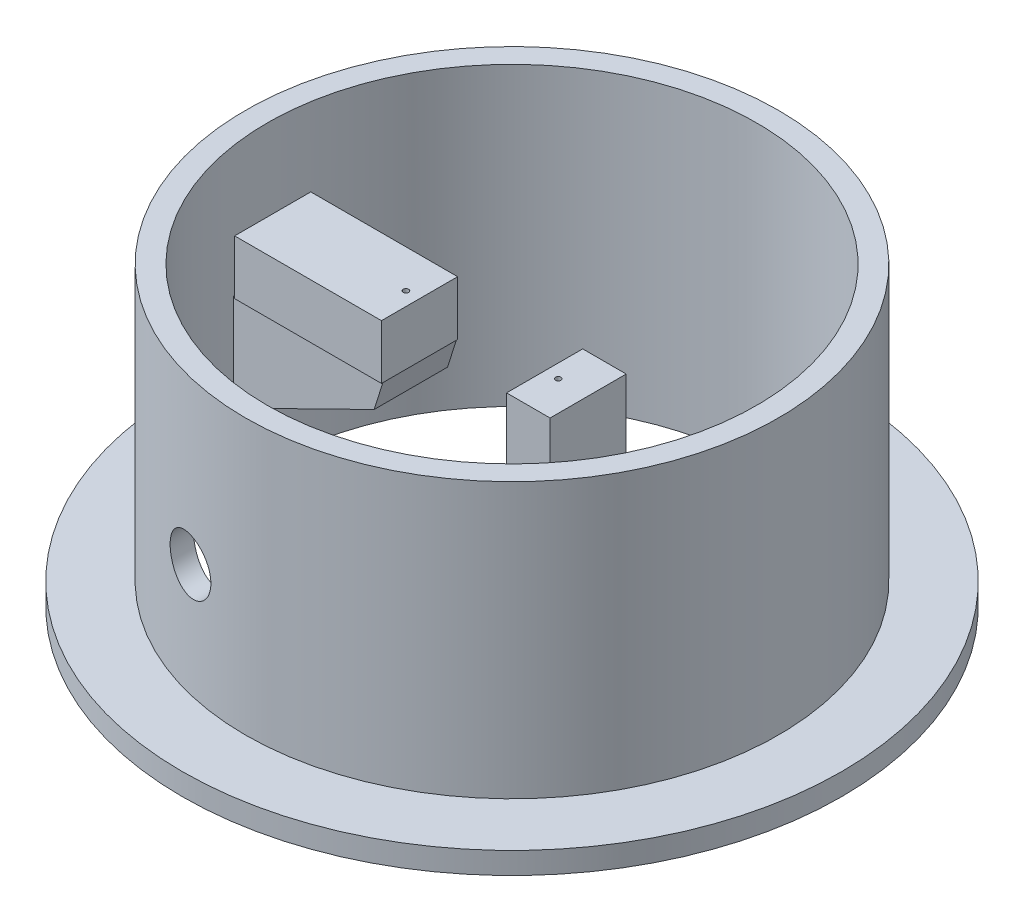
SolidWorks part; units mm, degrees
ref_plane "Front Plane" through (0, 0, 0) normal (0, 0, 1) x (1, 0, 0)
ref_plane "Top Plane" through (0, 0, 0) normal (0, 1, 0) x (1, 0, 0)
ref_plane "Right Plane" through (0, 0, 0) normal (1, 0, 0) x (0, 0, -1)
sketch "Sketch1" plane through (0, 0, 0) normal (0, 1, 0) x (1, 0, 0)
  circle A0 centre (0, 0) radius 60.625
  circle A1 centre (0, 0) radius 45
  dimension "D1" = 121.25
  dimension "D2" = 90
extrude "Boss-Extrude1" add sketch "Sketch1" along normal blind 4
sketch "Sketch2" plane through (0, 4, 0) normal (0, 1, 0) x (1, 0, 0)
  circle A0 centre (0, 0) radius 45 construction
  circle A1 centre (0, 0) radius 45
  circle A2 centre (0, 0) radius 49
  dimension "D1" = 4
extrude "Boss-Extrude2" add sketch "Sketch2" along normal blind 50.5
ref_plane "Plane1" through (0, 34.5, 0) normal (0, 1, 0) x (1, 0, 0)
sketch "Sketch4" plane through (0, 0, 0) normal (0, 0, 1) x (1, 0, 0)
  line L0 (-60.625, 0) -> (60.625, 0) construction
  line L1 (6, 40.5) -> (14, 40.5)
  line L2 (6, 40.5) -> (6, 0)
  line L3 (6, 0) -> (14, 0)
  line L4 (14, 40.5) -> (14, 0)
  line L5 (49, 54.5) -> (-49, 54.5) construction
  line L6 (-45, 54.5) -> (-45, 4)
  line L7 (-17, 40.5) -> (-44, 40.5)
  line L8 (-17, 40.5) -> (-17, 30.5)
  line L9 (-17, 30.5) -> (-44, 30.5)
  line L10 (-44, 40.5) -> (-44, 30.5)
  line L11 (60.625, 4) -> (-60.625, 4) construction
  line L12 (-17, 30.5) -> (-45, 2.5)
  dimension "D1" = 6
  dimension "D2" = 8
  dimension "D3" = 14
  dimension "D4" = 23
  dimension "D5" = 27
  dimension "D6" = 10
  dimension "D7" = 45
  dimension "D8" = 14
extrude "Boss-Extrude4" add sketch "Sketch4" along normal mid plane 14 contours L9 L8 L7 L6 | L12 L9 L6 | L1 L4 L3 L2 region at (-30.5, 35.5, 0)
sketch "Sketch5" plane through (0, 0, 0.8324) normal (0, -1, 0) x (1, 0, 0)
  line L0 (0.9227, 14.5796) -> (36.1058, 30.1379)
  line L1 (0.9227, -16.0291) -> (36.6512, -32.9046)
  line L2 (0.9227, 14.5796) -> (0.9227, -16.0291)
  arc A1 (36.6512, -32.9046) -> (36.1058, 30.1379) centre (-2.8733, -1.7229) ccw
extrude "Boss-Extrude5" add sketch "Sketch5" against normal up to surface (4 mm away) contours L0 A1 L1 L2 up to face at (0, 4, 60.625)
sketch "Sketch6" plane through (0, 0, 0) normal (0, 0, 1) x (1, 0, 0)
  circle A0 centre (-11.8474, 24.4856) radius 5
extrude "Cut-Extrude2" cut sketch "Sketch6" along normal blind 52 contours A0
sketch "Sketch11" plane through (0, 4, 0) normal (0, 1, 0) x (1, 0, 0)
  line L0 (16.2655, 12.7324) -> (16.2655, -6.5497)
  line L1 (16.2655, -6.5497) -> (5.715, -6.5497)
  line L2 (5.715, -6.5497) -> (5.715, -11.643)
  line L3 (5.715, -11.643) -> (30.818, -22.5574)
  line L4 (16.2655, 12.7324) -> (32.152, 20.615)
  arc A0 (32.152, 20.615) -> (30.818, -22.5574) centre (5.8984, -0.1806) cw
extrude "Cut-Extrude6" cut sketch "Sketch11" against normal through all
sketch "Sketch14" plane through (0, 54.5, 0) normal (0, 1, 0) x (1, 0, 0)
  line L0 (0, 45) -> (0, -65.3775) construction
  line L1 (-49, 0) -> (78.814, 0) construction
  circle A0 centre (0, 0) radius 45 construction
  circle A1 centre (0, 0) radius 49 construction
  circle A2 centre (0, 0) radius 49 construction
sketch "Sketch15" plane through (0, 40.5, 0) normal (0, 1, 0) x (1, 0, 0)
  line L2 (-49, 0) -> (78.814, 0) construction
  line L3 (-17, -7) -> (-17, 7) construction
  line L4 (6, -6.5497) -> (6, 7) construction
  circle A2 centre (-19.5, 0) radius 0.5
  circle A3 centre (8.5, 0) radius 0.5
  dimension "D1" = 1
  dimension "D2" = 1
  dimension "D3" = 2.5
  dimension "D4" = 2.5
extrude "Cut-Extrude7" cut sketch "Sketch15" against normal blind 4.5
extrude "Cut-Extrude8" cut sketch "Sketch15<3>" against normal blind 4.5
sketch "Sketch15<3>" plane through (0, 40.5, 0) normal (0, 1, 0) x (1, 0, 0) same geometry as "Sketch15"
sketch "Sketch17" plane through (0, 0, 0) normal (0, 0, 1) x (1, 0, 0)
  line L0 (-17, 30.5) -> (-45, 30.5)
  line L1 (-45, 54.5) -> (-45, 0) construction
  line L2 (-45, 30.5) -> (-45, 12.4458)
  line L3 (-45, 12.4458) -> (-18.5901, 25.4335)
  line L4 (-18.5901, 25.4335) -> (-17, 30.5)
extrude "Boss-Extrude6" add sketch "Sketch17" along normal mid plane 13.5
